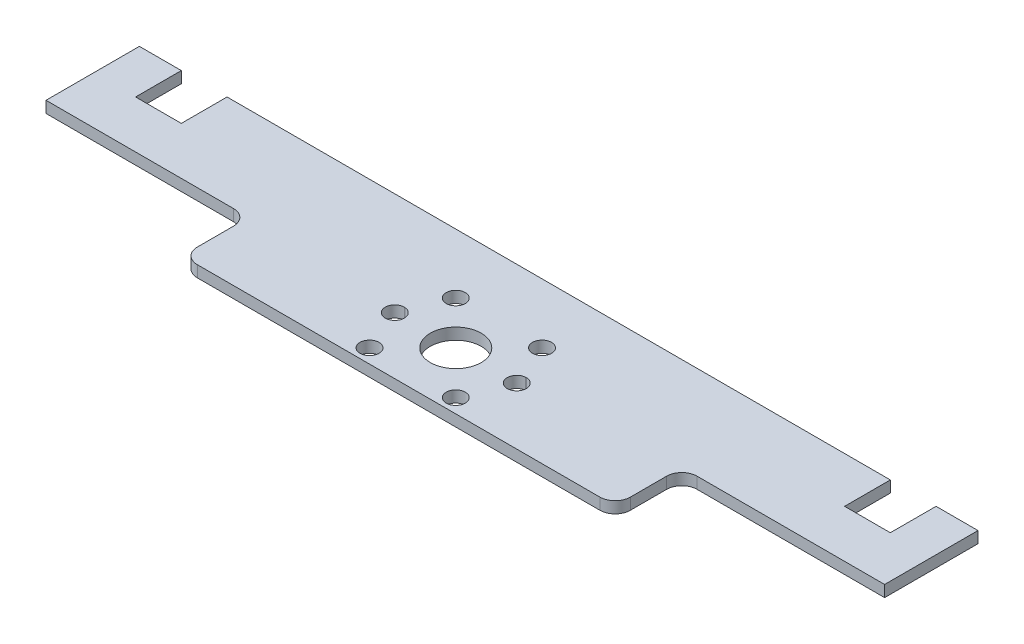
SolidWorks part; units mm, degrees
ref_plane "前视基准面" through (0, 0, 0) normal (0, 0, 1) x (1, 0, 0)
ref_plane "上视基准面" through (0, 0, 0) normal (0, 1, 0) x (1, 0, 0)
ref_plane "右视基准面" through (0, 0, 0) normal (1, 0, 0) x (0, 0, -1)
other "Configuration Table"
sketch "草图2" plane through (0, 0, 0) normal (0, 1, 0) x (1, 0, 0)
  line L0 (110, -9.2483) -> (-110, -9.2483)
  line L1 (110, -26.7483) -> (-110, -26.7483)
  line L2 (110, -26.7483) -> (110, 15.2517)
  line L3 (110, 15.2517) -> (-110, 15.2517)
  line L4 (-110, -26.7483) -> (-110, 15.2517)
  line L5 (-99, 15.2517) -> (-99, 3.2517)
  line L6 (-99, 3.2517) -> (-87, 3.2517)
  line L7 (56.8055, -9.2483) -> (56.8055, -26.7483)
  line L8 (0, -9.2483) -> (0, 15.2517)
  line L9 (-56.8055, -9.2483) -> (-56.8055, -26.7483)
  line L10 (-87, 3.2517) -> (-87, 15.2517)
  line L11 (87, 3.2517) -> (87, 15.2517)
  line L12 (99, 3.2517) -> (87, 3.2517)
  line L13 (99, 15.2517) -> (99, 3.2517)
  circle A0 centre (0, -11.7483) radius 6.682
  circle A1 centre (11.3137, -0.4346) radius 2.5
  circle A2 centre (0, -11.7483) radius 16
  circle A3 centre (16, -11.7483) radius 2.5
  circle A4 centre (11.3137, -23.062) radius 2.5
  circle A5 centre (0, -27.7483) radius 2.5
  circle A6 centre (-11.3137, -23.062) radius 2.5
  circle A7 centre (-16, -11.7483) radius 2.5
  circle A8 centre (-11.3137, -0.4346) radius 2.5
  circle A9 centre (0, 4.2517) radius 2.5
  point P0 (0, 0)
  point P37 (0, -11.7483)
  dimension "D3" = 5
  dimension "D1" = 220
  dimension "D2" = 17.5
  dimension "D5" = 42
  dimension "D6" = 11
  dimension "D7" = 23
  dimension "D8" = 12
  dimension "D4" = 8
extrude "凸台-拉伸1" add sketch "草图2" along normal blind 3 contours A7 A2 A6 L1 A5 A4 A3 L0 A0 | A9 L8 A0 L0 A2 A1 | A9 A2 A8 L0 A0 L8 | A9 L8 L3 L4 L0 A2 A8 | A9 A2 A1 L0 L2 L3 L8 | L1 A5 | A4 A2 L1 L7 L0 A3 | A7 L0 L9 L1 A2 A6 | A9 region at (56.2872, 0, -3.0768) region at (35.6553, 0, 18.309) region at (15.4472, 0, 9.3085) region at (6.9935, 0, 3.4384) region at (0, 0, 26.1296) region at (-56.2872, 0, -3.0768) region at (-6.9935, 0, 3.4384) region at (-35.6553, 0, 18.309)
fillet "圆角1" radius 4 4 edges at (56.8055, 1.5, 9.2483) (56.8055, 1.5, 26.7483) (-56.8055, 1.5, 9.2483) (-56.8055, 1.5, 26.7483)
